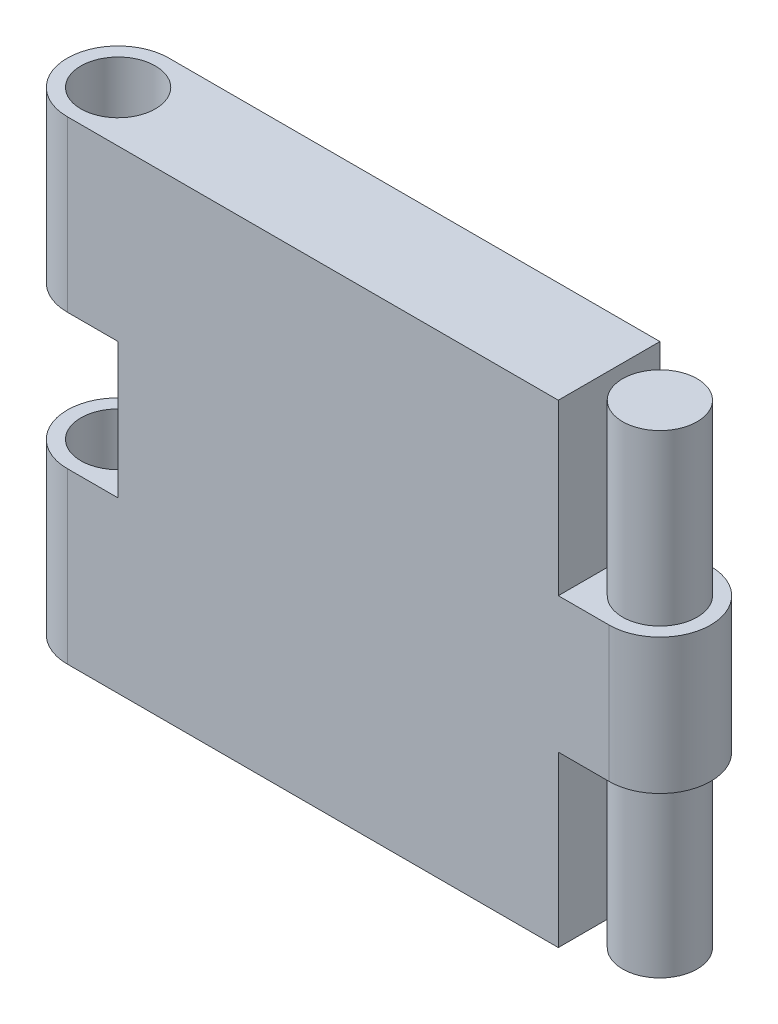
SolidWorks part; units mm, degrees
ref_plane "Front Plane" through (0, 0, 0) normal (0, 0, 1) x (1, 0, 0)
ref_plane "Top Plane" through (0, 0, 0) normal (0, 1, 0) x (1, 0, 0)
ref_plane "Right Plane" through (0, 0, 0) normal (1, 0, 0) x (0, 0, -1)
sketch "Plate Sketch" plane through (0, 0, 0) normal (0, 0, 1) x (1, 0, 0)
  line L1 (-40, 35) -> (40, 35)
  line L2 (-40, 35) -> (-40, -35)
  line L3 (-40, -35) -> (40, -35)
  line L4 (40, 35) -> (40, -35)
  line L5 (-40, 35) -> (40, -35) construction
  line L6 (-40, -35) -> (40, 35) construction
  point P0 (0, 0)
  dimension "D1" = 70
  dimension "D2" = 80
extrude "Plate Extrude" add sketch "Plate Sketch" against normal blind 15
sketch "Hole Sketch" plane through (0, 0, 0) normal (0, 1, 0) x (1, 0, 0)
  line L0 (-32.5, 15) -> (-32.5, 0) construction
  line L1 (40, 15) -> (-40, 15) construction
  line L2 (40, 0) -> (-40, 0) construction
  line L3 (-38, 7.5) -> (-40, 7.5) construction
  line L4 (-40, 15) -> (-40, 0) construction
  circle A0 centre (-32.5, 7.5) radius 5.5
  point P5 (-32.5, 7.5)
  dimension "D1" = 11
  dimension "D2" = 2
extrude "Hole Cut" cut sketch "Hole Sketch" along normal up to surface and the other way up to surface up to face at (0, 35, -7.5) other way up to face at (0, -35, -7.5)
fillet "Female Fillet" 2 edges at (-40, 0, 0) (-40, 0, -15) type full round first side face at (0, 0, 0) second side face at (0, 0, -15) middle face at (-40, 0, -7.5)
sketch "Gap Sketch" plane through (0, 0, 0) normal (0, 1, 0) x (1, 0, 0)
  line L0 (40, 15) -> (-32.5, 15) construction
  line L1 (-40, 15) -> (-25, 15)
  line L2 (-40, 15) -> (-40, 0)
  line L3 (-40, 0) -> (-25, 0)
  line L4 (-25, 15) -> (-25, 0)
  line L5 (-40, 15) -> (-25, 0) construction
  line L6 (-40, 0) -> (-25, 15) construction
  line L7 (40, 0) -> (-32.5, 0) construction
  line L8 (-27, 7.5) -> (-25, 7.5) construction
  arc A0 (-32.5, 15) -> (-32.5, 0) centre (-32.5, 7.5) ccw construction
  circle A1 centre (-32.5, 7.5) radius 5.5 construction
  point P0 (-32.5, 7.5)
  dimension "D1" = 2
extrude "Gap Cut" cut sketch "Gap Sketch" against normal blind 10 and the other way blind 10
sketch "Pin Support Sketch" plane through (0, 0, 0) normal (0, 1, 0) x (1, 0, 0)
  line L0 (40, 15) -> (-32.5, 15) construction
  line L1 (40, 15) -> (55, 15)
  line L2 (40, 15) -> (40, 0)
  line L3 (40, 0) -> (55, 0)
  line L4 (55, 15) -> (55, 0)
  line L5 (40, 15) -> (55, 0) construction
  line L6 (40, 0) -> (55, 15) construction
  line L7 (40, 0) -> (-32.5, 0) construction
  line L8 (40, 15) -> (40, 0) construction
  point P0 (47.5, 7.5)
extrude "Pin Support Extrude" add sketch "Pin Support Sketch" along normal blind 10 and the other way blind 10
sketch "Pin Sketch" plane through (0, 10, 0) normal (0, 1, 0) x (1, 0, 0)
  circle A0 centre (47.5, 7.5) radius 5.5
  dimension "D1" = 11
extrude "Pin Extrude" add sketch "Pin Sketch" along normal up to surface and the other way up to surface up to face at (-32.5, 35, -2) other way up to face at (-32.5, -35, -13)
fillet "Male Fillet" 2 edges at (55, 0, -15) (55, 0, 0) type full round first side face at (7.5, 0, -15) second side face at (7.5, 0, 0) middle face at (55, 0, -7.5)
